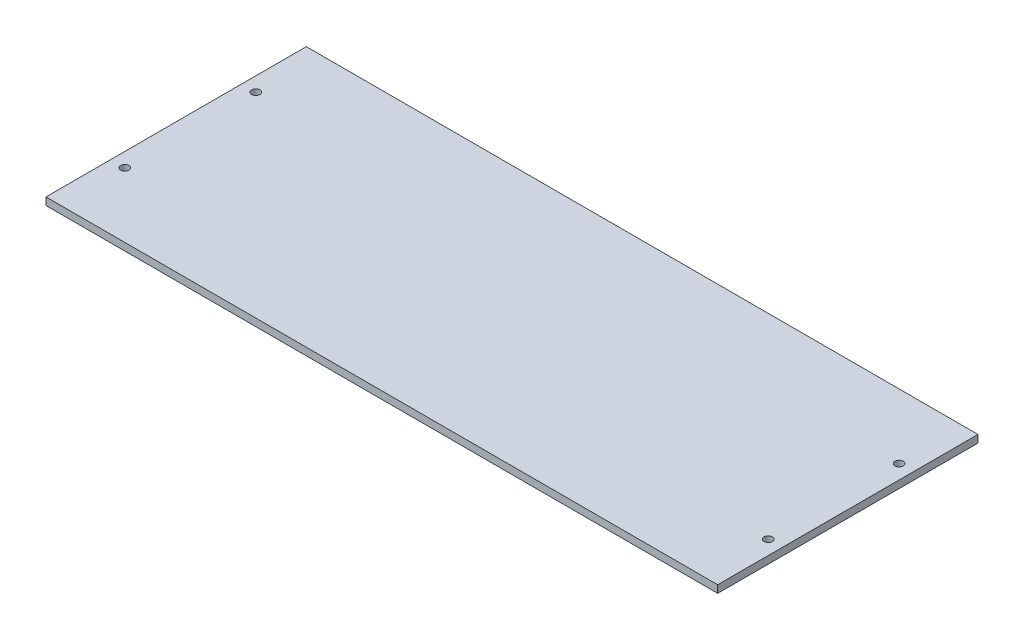
SolidWorks part; units mm, degrees
ref_plane "前视基准面" through (0, 0, 0) normal (0, 0, 1) x (1, 0, 0)
ref_plane "上视基准面" through (0, 0, 0) normal (0, 1, 0) x (1, 0, 0)
ref_plane "右视基准面" through (0, 0, 0) normal (1, 0, 0) x (0, 0, -1)
other "Configuration Table"
sketch "草图1" plane through (0, 0, 0) normal (0, 1, 0) x (1, 0, 0)
  line L0 (-94.7802, 0) -> (105.2085, 0) construction
  line L1 (-89.8, -34.8) -> (89.8, -34.8)
  line L2 (-89.8, -34.8) -> (-89.8, 34.8)
  line L3 (-89.8, 34.8) -> (89.8, 34.8)
  line L4 (89.8, -34.8) -> (89.8, 34.8)
  line L5 (-89.8, -34.8) -> (89.8, 34.8) construction
  line L6 (-89.8, 34.8) -> (89.8, -34.8) construction
  line L7 (0, 72.1386) -> (0, -72.7943) construction
  circle A0 centre (-86, 17.5) radius 1.1
  circle A1 centre (-86, -17.5) radius 1.1
  circle A2 centre (86, -17.5) radius 1.1
  circle A3 centre (86, 17.5) radius 1.1
  point P0 (0, 0)
  dimension "D3" = 2.2
  dimension "D4" = 35
  dimension "D5" = 172
  dimension "D1" = 69.6
  dimension "D2" = 179.6
extrude "凸台-拉伸1" add sketch "草图1" along normal blind 2
